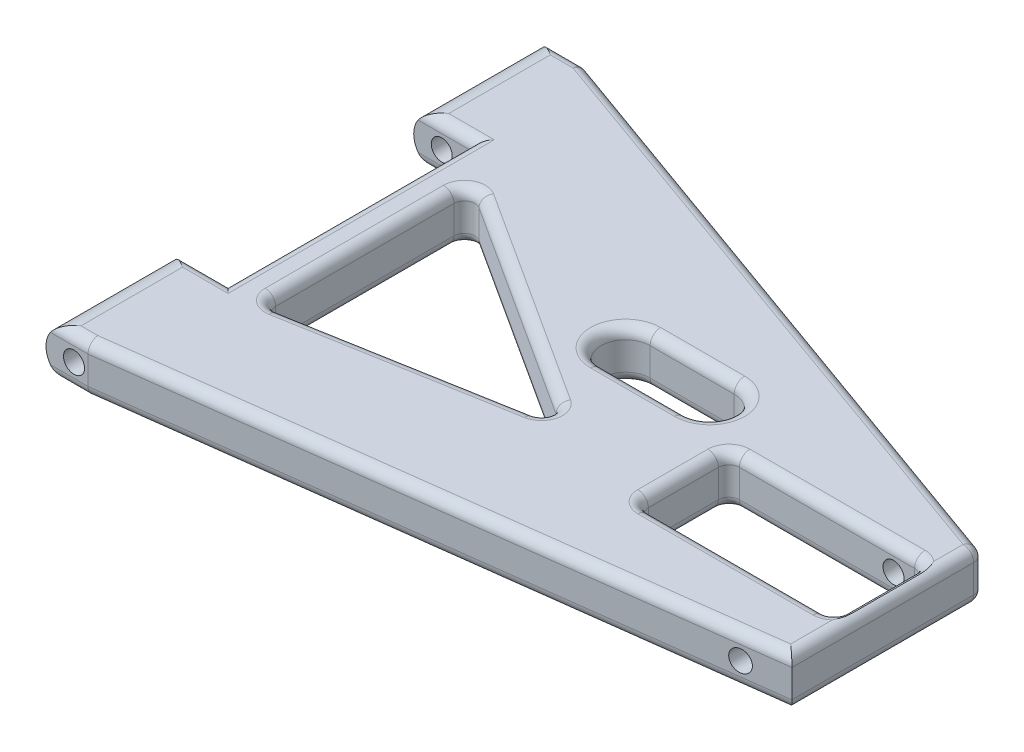
SolidWorks part; units mm, degrees
ref_plane "Front Plane" through (0, 0, 0) normal (0, 0, 1) x (1, 0, 0)
ref_plane "Top Plane" through (0, 0, 0) normal (0, 1, 0) x (1, 0, 0)
ref_plane "Right Plane" through (0, 0, 0) normal (1, 0, 0) x (0, 0, -1)
sketch "A_Arm_Sketch" plane through (0, 0, 0) normal (0, 1, 0) x (1, 0, 0)
  line L0 (47.5, 3.5) -> (47.5, -23.5)
  line L1 (-47.5, 35) -> (47.5, 35) construction
  line L2 (-47.5, 35) -> (-47.5, -35)
  line L3 (-47.5, -35) -> (47.5, -35) construction
  line L4 (47.5, 35) -> (47.5, -35) construction
  line L5 (-47.5, 35) -> (47.5, -35) construction
  line L6 (-47.5, -35) -> (47.5, 35) construction
  line L8 (17.5008, -23.5) -> (-47.5, -35) construction
  line L9 (-47.5, 17.5) -> (-47.5, -17.5)
  line L11 (-47.5, 0) -> (47.5, -10) construction
  line L13 (2.7473, -5.2892) -> (3.5847, 2.6669) construction
  line L14 (-2.4153, 2.6669) -> (9.5847, 2.6669)
  line L15 (-2.4153, 2.6669) -> (9.5847, 2.6669) construction
  line L16 (-2.4153, 6.1669) -> (9.5847, 6.1669)
  line L17 (-2.4153, -0.8331) -> (9.5847, -0.8331)
  line L19 (17.5008, -15.5) -> (17.5008, -23.5) construction
  line L24 (17.5008, -23.5) -> (47.5, -23.5) construction
  line L25 (-47.5, 35) -> (-40.5, 35)
  line L26 (17.5008, -2.5) -> (45.5008, -2.5)
  line L27 (17.5008, -2.5) -> (17.5008, -15.5)
  line L28 (17.5008, -15.5) -> (45.5008, -15.5)
  line L29 (45.5008, -2.5) -> (45.5008, -15.5)
  line L30 (-40.5, 35) -> (47.5, 3.5)
  line L34 (-47.5, 17.5) -> (-39, 17.5)
  line L36 (-39, 17.5) -> (-39, -17.5)
  line L37 (-34, 12.5) -> (-34, -17.5)
  line L38 (-34, -17.5) -> (2.5, -11.0424)
  line L39 (-47.5, -17.5) -> (-39, -17.5)
  line L40 (-34, 12.5) -> (2.5, -11.0424)
  line L41 (-47.5, -35) -> (47.5, -23.5) construction
  line L42 (-47.5, -35) -> (-41.5, -35)
  line L43 (-41.5, -35) -> (47.5, -23.5)
  arc A3 (-2.4153, 6.1669) -> (-2.4153, -0.8331) centre (-2.4153, 2.6669) ccw
  arc A4 (9.5847, -0.8331) -> (9.5847, 6.1669) centre (9.5847, 2.6669) ccw
  point P0 (0, 0)
  point P9 (47.5, -10)
  point P12 (47.5, -10)
  point P13 (-47.5, 0)
  point P19 (3.5847, 2.6669)
  point P22 (3.5847, 2.6669)
  dimension "D7" = 50
  dimension "D8" = 8
  dimension "D11" = 8
  dimension "D18" = 30
  dimension "D16" = 5
  dimension "D1" = 95
  dimension "D2" = 70
  dimension "D3" = 25
  dimension "D4" = 28
  dimension "D5" = 13.5
  dimension "D6" = 35
  dimension "D9" = 45
  dimension "D10" = 12
  dimension "D12" = 29.9992
  dimension "D13" = 27.0001
  dimension "D14" = 7
  dimension "D15" = 13
  dimension "D17" = 8.5
extrude "Main_Extrude" add sketch "A_Arm_Sketch" along normal blind 7 contours L2 L8 L24 L0 L28 L27 L26 A4 L17 A3 L16 region at (-6.2529, 0, 3.5461)
fillet "Complete_Fillet" radius 1.5 47 edges at (-5.9153, 0, -2.6669) (3.5847, 0, -6.1669) (13.0847, 0, -2.6669) (-5.9153, 7, -2.6669) (3.5847, 7, -6.1669) (13.0847, 7, -2.6669) (31.5008, 0, 15.5) (31.5008, 0, 2.5) (17.5008, 0, 9) (31.5008, 7, 2.5) (31.5008, 7, 15.5) (17.5008, 7, 9) (3.5847, 0, 0.8331) (3.5847, 7, 0.8331) (47.5, 0, 10) (47.5, 7, 10) (17.5008, 3.5, 15.5) (17.5008, 3.5, 2.5) (45.5008, 3.5, 15.5) (45.5008, 3.5, 2.5) (45.5008, 0, 9) (45.5008, 7, 9) (-44, 0, -35) (-44, 7, -35) (-40.5, 3.5, -35) (47.5, 3.5, -3.5) (3.5, 0, -19.25) (3.5, 7, -19.25) (-15.75, 7, 14.2712) (-15.75, 0, 14.2712) (-43.25, 0, -17.5) (-43.25, 7, -17.5) (-34, 7, 2.5) (-34, 0, 2.5) (-34, 3.5, 17.5) (-39, 7, 0) (-39, 0, 0) (-15.75, 7, -0.7288) (-15.75, 0, -0.7288) (-34, 3.5, -12.5) (2.5, 3.5, 11.0424) (-43.25, 0, 17.5) (-43.25, 7, 17.5) (-44.5, 0, 35) (-44.5, 7, 35) (3, 0, 29.25) (3, 7, 29.25)
fillet "Fillet2" radius 3.5 4 edges at (-47.5, 0, -26.25) (-47.5, 7, -26.25) (-47.5, 0, 26.25) (-47.5, 7, 26.25) tangent propagation no
sketch "Sketch1" plane through (0, 0, 2.5) normal (0, 0, 1) x (1, 0, 0)
  line L0 (44.0008, 3.5) -> (19.0008, 3.5) construction
  line L1 (44.0008, 1.5) -> (44.0008, 5.5) construction
  line L2 (19.0008, 5.5) -> (19.0008, 1.5) construction
  circle A0 centre (41.0008, 3.5) radius 1.5
  dimension "D1" = 3
  dimension "D2" = 3
extrude "Cut-Extrude1" cut sketch "Sketch1" against normal through all both and the other way through all
sketch "Sketch2" plane through (0, 0, -17.5) normal (0, 0, 1) x (1, 0, 0)
  line L0 (-47.5, 3.5) -> (-39, 3.5) construction
  line L1 (-39, 5.5) -> (-39, 1.5) construction
  circle A0 centre (-43.5, 3.5) radius 1.5
  dimension "D1" = 4.5
extrude "Cut-Extrude2" cut sketch "Sketch2" against normal through all both and the other way through all
